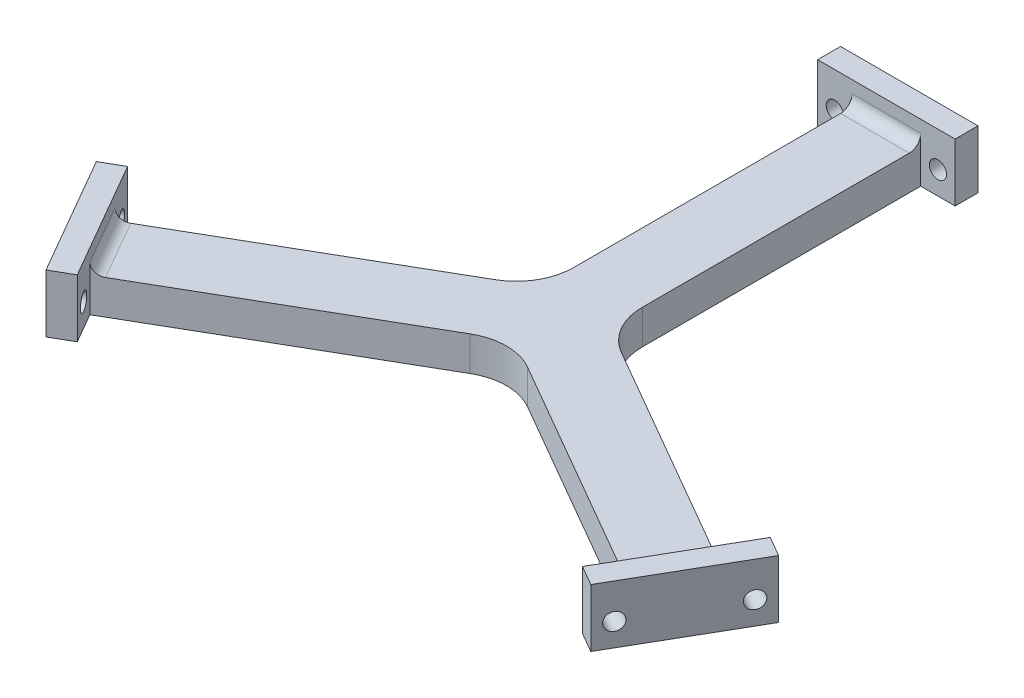
SolidWorks part; units mm, degrees
ref_plane "前视基准面" through (0, 0, 0) normal (0, 0, 1) x (1, 0, 0)
ref_plane "上视基准面" through (0, 0, 0) normal (0, 1, 0) x (1, 0, 0)
ref_plane "右视基准面" through (0, 0, 0) normal (1, 0, 0) x (0, 0, -1)
sketch "草图1" plane through (0, 0, 0) normal (0, 1, 0) x (1, 0, 0)
  line L1 (-6, 61.85) -> (6, 61.85)
  line L2 (-6, 61.85) -> (-6, 0)
  line L3 (-6, 0) -> (6, 0)
  line L4 (6, 61.85) -> (6, 0)
  dimension "D1" = 12
  dimension "D2" = 61.85
  dimension "D3" = 6
  dimension "D4" = 0
extrude "凸台-拉伸1" add sketch "草图1" along normal blind 6
ref_axis "基准轴1" through (0, 6.3, 0) along (0, -1, 0)
sketch "草图2" plane through (0, 0, -61.85) normal (0, 0, -1) x (-1, 0, 0)
  line L1 (-12, 10.13) -> (12, 10.13)
  line L2 (-12, 10.13) -> (-12, 0)
  line L3 (-12, 0) -> (12, 0)
  line L4 (12, 10.13) -> (12, 0)
  line L5 (-12, 10.13) -> (12, 0) construction
  line L6 (-12, 0) -> (12, 10.13) construction
  point P0 (0, 5.065)
  dimension "D1" = 5.065
  dimension "D2" = 10.13
  dimension "D3" = 0
  dimension "D4" = 24
extrude "凸台-拉伸2" add sketch "草图2" against normal blind 4
sketch "草图3" plane through (0, 0, -57.85) normal (0, 0, 1) x (1, 0, 0)
  line L0 (-6, 0) -> (-12, 0) construction
  line L1 (-12, 0) -> (-12, 10.13) construction
  line L2 (12, 10.13) -> (12, 0) construction
  line L3 (12, 0) -> (6, 0) construction
  circle A1 centre (-9, 4) radius 1.5
  circle A2 centre (9, 4) radius 1.5
  dimension "D1" = 3
  dimension "D2" = 3
  dimension "D4" = 4
  dimension "D5" = 3
  dimension "D6" = 3
  dimension "D7" = 4
extrude "切除-拉伸1" cut sketch "草图3" against normal blind 4
fillet "圆角1" radius 2 1 edges at (0, 6, -57.85)
pattern_circular "阵列(圆周)1" count 3 over 360 about axis through (0, 6.3, 0) along (0, -1, 0) of "凸台-拉伸1", "凸台-拉伸2", "切除-拉伸1", "圆角1"
fillet "圆角2" radius 10 3 edges at (-6, 3, -3.4641) (6, 3, -3.4641) (0, 3, 6.9282)
